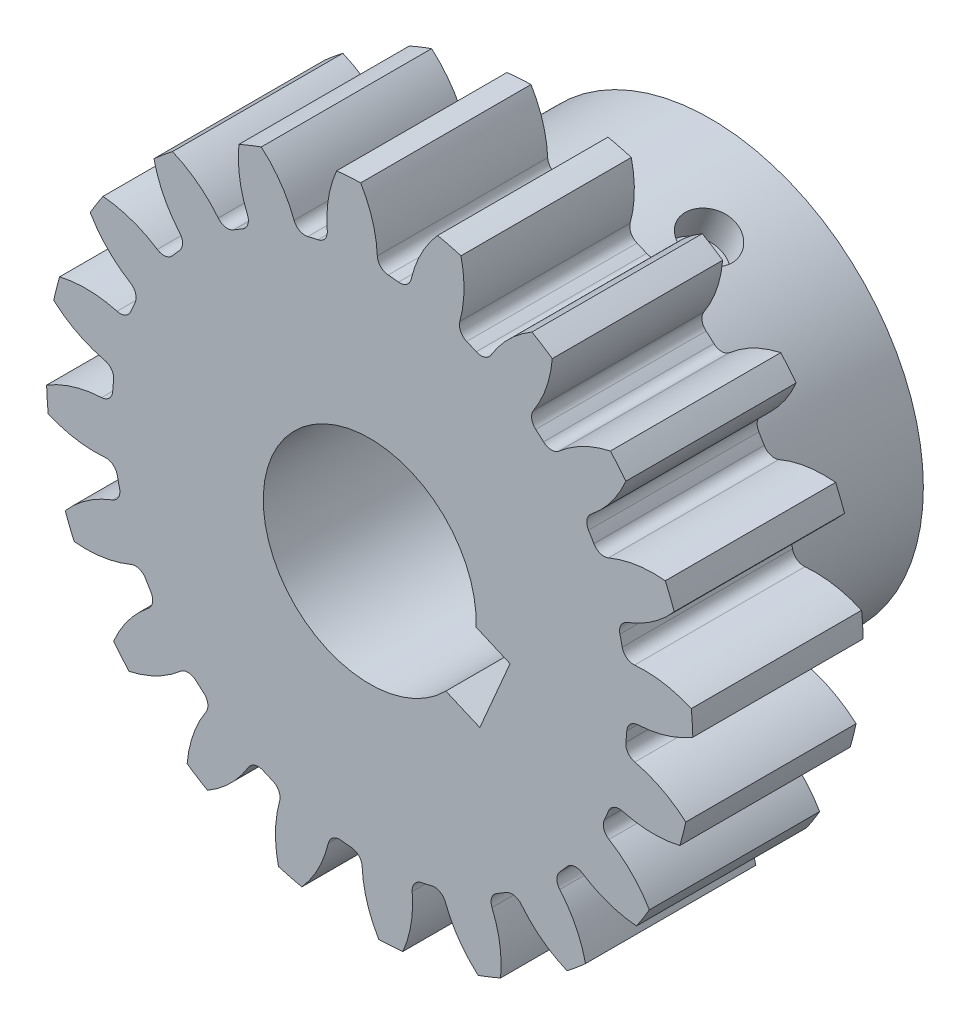
SolidWorks part; units mm, degrees
ref_plane "Front" through (0, 0, 0) normal (0, 0, 1) x (1, 0, 0)
ref_plane "Top" through (0, 0, 0) normal (0, 1, 0) x (1, 0, 0)
ref_plane "Right" through (0, 0, 0) normal (1, 0, 0) x (0, 0, -1)
sketch "Sketch3" plane through (0, 0, 0) normal (0, 0, 1) x (1, 0, 0)
  circle A0 centre (0, 0) radius 18.9745
  dimension "od" = 37.9491
extrude "gearBody" add sketch "Sketch3" along normal blind 10
sketch "Sketch2" plane through (0, 0, 0) normal (0, 0, 1) x (1, 0, 0)
  line L0 (0, 0) -> (15.4289, 6.3909) construction
  line L1 (20.2666, -6.3399) -> (0, 0) construction
  line L2 (0, 0) -> (36.3143, 0) construction
  line L3 (17.2483, -0.2074) -> (16.9964, -2.9444) construction
  line L5 (17.1224, -1.5759) -> (0, 0) construction
  line L7 (0, 0) -> (16.7001, 0) construction
  arc A0 (16.6968, -0.3352) -> (16.4775, -2.7181) centre (0, 0) ccw construction
  arc A1 (18.9671, 0.5318) -> (18.5514, -3.9849) centre (0, 0) ccw construction
  arc A2 (17.2483, -0.2074) -> (16.9964, -2.9444) centre (0, 0) ccw construction
  arc A3 (15.034, -1.6914) -> (15.0901, -1.0811) centre (0, 0) ccw
  arc A4 (20.2666, -6.3399) -> (15.5585, -2.4342) centre (14.0032, -9.0997) ccw
  arc A5 (20.2666, -6.3399) -> (21.0834, 2.5342) centre (0, 0) ccw
  arc A6 (21.0834, 2.5342) -> (15.7414, -0.4465) centre (15.4289, 6.3909) cw
  arc A7 (15.0901, -1.0811) -> (15.7414, -0.4465) centre (15.7727, -1.13) cw
  arc A8 (15.5585, -2.4342) -> (15.034, -1.6914) centre (15.7139, -1.7679) cw
  point P6 (21.0834, 2.5342)
  point P22 (20.2666, -6.3399)
  dimension "baseDia" = 33.4003
  dimension "od" = 37.9491
  dimension "pd" = 34.4992
  dimension "rd" = 30.2577
  dimension "rFillet" = 0.6843
  dimension "pointX" = 21.0834
  dimension "pointY" = 2.5342
  dimension "CTT" = 2.737
  dimension "flankCenterAngle" = 22.5
extrude "toothCut" cut sketch "Sketch2" along normal through all
pattern_circular "CirPattern1" count 20 over 360 about axis through (0, 0, 10) along (0, 0, -1) of "toothCut"
ref_axis "toothSpace" through (0, 0, 0) along (0.9958, -0.0916, 0)
ref_axis "Axis2" through (18.39, -4.6734, 0) along (-0.9692, 0.2463, 0)
sketch "hub1Dia" plane through (0, 0, 0) normal (0, 0, -1) x (-1, 0, 0)
  circle A0 centre (0, 0) radius 12.5
  dimension "hub1Dia" = 25
extrude "hub1" add sketch "hub1Dia" along normal blind 10
sketch "hub2Dia" plane through (0, 0, 10) normal (0, 0, 1) x (1, 0, 0)
  circle A0 centre (0, 0) radius 0.5
  dimension "hub2dia" = 1
sketch "boreDia" plane through (0, 0, 0) normal (0, 0, 1) x (1, 0, 0)
  circle A0 centre (0, 0) radius 6.25
  dimension "boreDia" = 12.5
extrude "bore" cut sketch "boreDia" against normal mid plane 25400
sketch "kwy1sketch" plane through (0, 0, 0) normal (0, 0, 1) x (1, 0, 0)
  line L0 (-4.8404, 2.0804) -> (0, 0) construction
  line L1 (8.2383, -1.0919) -> (6.4614, -5.2262)
  line L2 (6.4614, -5.2262) -> (1.8677, -3.2518)
  line L3 (8.2383, -1.0919) -> (3.6447, 0.8825)
  line L4 (1.8677, -3.2518) -> (0, 0)
  line L5 (0, 0) -> (3.6447, 0.8825)
  line L6 (0, 0) -> (15.0652, -1.3865) construction
  line L7 (7.3499, -3.159) -> (0, 0) construction
  arc A7 (15.034, -1.6914) -> (15.0901, -1.0811) centre (0, 0) ccw construction
  point P9 (7.3499, -3.159)
  point P13 (-0.8074, 0.347)
  dimension "kwy1width" = 4.5
  dimension "kwy1depth" = 8
  dimension "kwy1angle" = 18
  dimension "kwy1Depth2" = 5
extrude "kwy1" cut sketch "kwy1sketch" against normal mid plane 12700
sketch "kwy2sketch" plane through (0, 0, 0) normal (0, 0, 1) x (1, 0, 0)
  line L0 (15.0652, -1.3865) -> (0, 0) construction
  line L1 (0, 0) -> (-3.3818, -1.3486) construction
  line L2 (6.6901, 4.8211) -> (8.1718, 1.1056)
  line L3 (8.1718, 1.1056) -> (3.5274, -0.7465)
  line L4 (6.6901, 4.8211) -> (2.0458, 2.969)
  line L5 (3.5274, -0.7465) -> (0, 0)
  line L6 (0, 0) -> (2.0458, 2.969)
  arc A2 (15.034, -1.6914) -> (15.0901, -1.0811) centre (0, 0) ccw construction
  point P10 (7.4309, 2.9634)
  dimension "kwy2angle" = 27
  dimension "kwy2Width" = 4
  dimension "kwy2depth" = 8
  dimension "kwy2Depth2" = 5
sketch "kwy3sketch" plane through (0, 0, 0) normal (0, 0, 1) x (1, 0, 0)
  line L0 (15.0652, -1.3865) -> (0, 0) construction
  line L1 (0, 0) -> (-1.0401, -2.4199) construction
  line L2 (1.3216, 8.1396) -> (4.9965, 6.5601)
  line L3 (4.9965, 6.5601) -> (3.0221, 1.9664)
  line L4 (1.3216, 8.1396) -> (-0.6528, 3.546)
  line L5 (3.0221, 1.9664) -> (0, 0)
  line L6 (-0.6528, 3.546) -> (0, 0)
  point P10 (3.159, 7.3499)
  dimension "kwy3angle" = 72
  dimension "kwy3depth" = 8
  dimension "kwy3width" = 4
  dimension "kwy3Depth2" = 5
sketch "kwy4sketch" plane through (0, 0, 0) normal (0, 0, 1) x (1, 0, 0)
  line L0 (15.0652, -1.3865) -> (0, 0) construction
  line L1 (0, 0) -> (0.7629, -1.913) construction
  line L2 (-1.1056, 8.1718) -> (-4.8211, 6.6901)
  line L3 (-4.8211, 6.6901) -> (-2.969, 2.0458)
  line L4 (-2.969, 2.0458) -> (0, 0)
  line L5 (0.7465, 3.5274) -> (0, 0)
  line L6 (-1.1056, 8.1718) -> (0.7465, 3.5274)
  point P15 (-2.9634, 7.4309)
  dimension "kwy4angle" = 117
  dimension "kwy4depth" = 8
  dimension "kwy4width" = 4
  dimension "kwy4Depth2" = 5
sketch "kwy5sketch" plane through (0, 0, 0) normal (0, 0, 1) x (1, 0, 0)
  line L0 (15.0652, -1.3865) -> (0, 0) construction
  line L1 (0, 0) -> (1.625, -0.6984) construction
  line L2 (-6.5601, 4.9965) -> (-8.1396, 1.3216)
  line L3 (-8.1396, 1.3216) -> (-3.546, -0.6528)
  line L4 (-6.5601, 4.9965) -> (-1.9664, 3.0221)
  line L5 (-3.546, -0.6528) -> (0, 0)
  line L6 (-1.9664, 3.0221) -> (0, 0)
  point P10 (-7.3499, 3.159)
  dimension "kwy5width" = 4
  dimension "kwy5depth" = 8
  dimension "kwy5angle" = 162
  dimension "kwy5Depth2" = 5
sketch "kwy6sketch" plane through (0, 0, 0) normal (0, 0, 1) x (1, 0, 0)
  line L0 (15.0652, -1.3865) -> (0, 0) construction
  line L1 (0, 0) -> (1.6416, 0.6547) construction
  line L2 (-8.1718, -1.1056) -> (-6.6901, -4.8211)
  line L3 (-6.6901, -4.8211) -> (-2.0458, -2.969)
  line L4 (-8.1718, -1.1056) -> (-3.5274, 0.7465)
  line L5 (-2.0458, -2.969) -> (0, 0)
  line L6 (-3.5274, 0.7465) -> (0, 0)
  point P10 (-7.4309, -2.9634)
  dimension "kwy6angle" = 207
  dimension "kwy6width" = 4
  dimension "kwy6depth" = 8
  dimension "kwy6Depth2" = 5
sketch "kwy7sketch" plane through (0, 0, 0) normal (0, 0, 1) x (1, 0, 0)
  line L0 (15.0652, -1.3865) -> (0, 0) construction
  line L1 (0, 0) -> (0.7819, 1.8191) construction
  line L2 (-4.9965, -6.5601) -> (-1.3216, -8.1396)
  line L3 (-4.9965, -6.5601) -> (-3.0221, -1.9664)
  line L4 (-1.3216, -8.1396) -> (0.6528, -3.546)
  line L5 (-3.0221, -1.9664) -> (0, 0)
  line L6 (0.6528, -3.546) -> (0, 0)
  point P10 (-3.159, -7.3499)
  dimension "kwy7angle" = 72
  dimension "kwy7width" = 4
  dimension "kwy7depth" = 8
  dimension "kwy7angle1" = 252
  dimension "kwy7Depth2" = 5
sketch "kwy8sketch" plane through (0, 0, 0) normal (0, 0, 1) x (1, 0, 0)
  line L0 (15.0652, -1.3865) -> (0, 0) construction
  line L1 (0, 0) -> (-0.6516, 1.634) construction
  line L2 (1.1056, -8.1718) -> (4.8211, -6.6901)
  line L3 (4.8211, -6.6901) -> (2.969, -2.0458)
  line L4 (1.1056, -8.1718) -> (-0.7465, -3.5274)
  line L5 (2.969, -2.0458) -> (0, 0)
  line L6 (-0.7465, -3.5274) -> (0, 0)
  point P10 (2.9634, -7.4309)
  dimension "kwy8angle" = 297
  dimension "kwy8width" = 4
  dimension "kwy8depth" = 8
  dimension "kwy8Depth2" = 5
sketch "centerLine" plane through (0, 0, 0) normal (0, 1, 0) x (1, 0, 0)
  line L0 (0, 36.4807) -> (0, -59.6309) construction
ref_plane "CB1plane" through (0, 0, -10) normal (0, 0, -1) x (-1, 0, 0)
sketch "CB1diameter" plane through (0, 0, -10) normal (0, 0, -1) x (-1, 0, 0)
  circle A0 centre (0, 0) radius 0.5
  dimension "CB1diameter" = 1
ref_plane "CB2plane" through (0, 0, 10) normal (0, 0, 1) x (1, 0, 0)
sketch "CB2diameter" plane through (0, 0, 10) normal (0, 0, 1) x (1, 0, 0)
  circle A0 centre (0, 0) radius 0.5
  dimension "CB2diameter" = 1
ref_axis "Axis1" through (0, 0, 50) along (0, 0, -1)
hole_wizard "ss1Hub1" positions "ss1TriangleH1" profile "ss1SketchH1" hole size "Ø3.0" standard "ANSI Metric"
sketch3d "ss1TriangleH1"
  line L0 (0, 0, 0) -> (11.4842, -4.936, -5) construction
  line L1 (11.4842, -4.936, -5) -> (11.4842, -4.936, 0) construction
  line L2 (11.4842, -4.936, 0) -> (0, 0, 0) construction
  line L7 (11.4842, -4.936, 0) -> (0, 0, 0) construction
  line L21 (2.8339, -0.2608, 0) -> (0, 0, 0) construction
  line L22 (0, 0, 0) -> (15.0652, -1.3865, 0) construction
  circle A0 centre (0, 0, 0) radius 12.5 construction
  point P1 (11.4842, -4.936, -5)
  point P10 (0, 0, -12.5)
  dimension "ss1HeightH1" = 5
  dimension "ss1AngleH1" = 18
sketch "ss1SketchH1" plane through (11.4842, -4.936, -5) normal (0, 0, 1) x (0.3949, 0.9187, 0)
  line L0 (0, 0) -> (0, 13.4013)
  line L1 (0, 13.4013) -> (1.5, 12.5)
  line L2 (1.5, 12.5) -> (1.5, 0)
  line L5 (1.5, 0) -> (0, 0)
  line L10 (0, 13.4013) -> (-1.5, 12.5) construction
  line L11 (0, -6.35) -> (0, 107.95) construction
  dimension "Hole Dia." = 3
  dimension "Hole Depth" = 12.5
  dimension "Drill Angle" = 118
hole_wizard "ss3Hub1" positions "ss3TriangleH1" profile "ss3SketchH1" hole size "Ø3.0" standard "ANSI Metric"
sketch3d "ss3TriangleH1"
  line L0 (0, 0, 0) -> (4.936, 11.4842, -5) construction
  line L1 (4.936, 11.4842, -5) -> (4.936, 11.4842, 0) construction
  line L2 (4.936, 11.4842, 0) -> (0, 0, 0) construction
  line L6 (15.0652, -1.3865, 0) -> (0, 0, 0) construction
  line L9 (0, 0, 0) -> (15.0652, -1.3865, 0) construction
  circle A0 centre (0, 0, 0) radius 12.5 construction
  arc A2 (15.0901, -1.0811, 0) -> (15.034, -1.6914, 0) centre (0, 0, 0) ccw construction
  point P0 (4.936, 11.4842, -5)
  point P8 (0, 0, -12.5)
  point P27 (0, 0, -15.1288)
  dimension "ss3HeightH1" = 5
  dimension "ss3AngleH1" = 72
sketch "ss3SketchH1" plane through (4.936, 11.4842, -5) normal (0, 0, 1) x (-0.9187, 0.3949, 0)
  line L0 (0, 0) -> (0, 13.4013)
  line L1 (0, 13.4013) -> (1.5, 12.5)
  line L2 (1.5, 12.5) -> (1.5, 0)
  line L5 (1.5, 0) -> (0, 0)
  line L10 (0, 13.4013) -> (-1.5, 12.5) construction
  line L11 (0, -6.35) -> (0, 107.95) construction
  dimension "Hole Dia." = 3
  dimension "Hole Depth" = 12.5
  dimension "Drill Angle" = 118
sketch3d "3DSketch1" plane through (0, 0, 0) normal (0, 0, 1) x (1, 0, 0)
ref_plane "Plane1" through (3.1393, 7.3039, 0) normal (-0.3949, -0.9187, 0) x (-0.9187, 0.3949, 0)
sketch "Sketch4" plane through (3.1393, 7.3039, 0) normal (-0.3949, -0.9187, 0) x (-0.9187, 0.3949, 0)
  line L0 (12.5, 10) -> (-12.5, 10) construction
  line L1 (3.25, 10) -> (-3.25, 10)
  line L2 (3.25, 10) -> (3.25, 0)
  line L3 (3.25, 0) -> (-3.25, 0)
  line L4 (-3.25, 10) -> (-3.25, 0)
  line L5 (3.25, 10) -> (-3.25, 0) construction
  line L6 (3.25, 0) -> (-3.25, 10) construction
  point P0 (0, 5)
  dimension "D1" = 6.5
extrude "Cut-Extrude1" cut sketch "Sketch4" against normal blind 2.5
